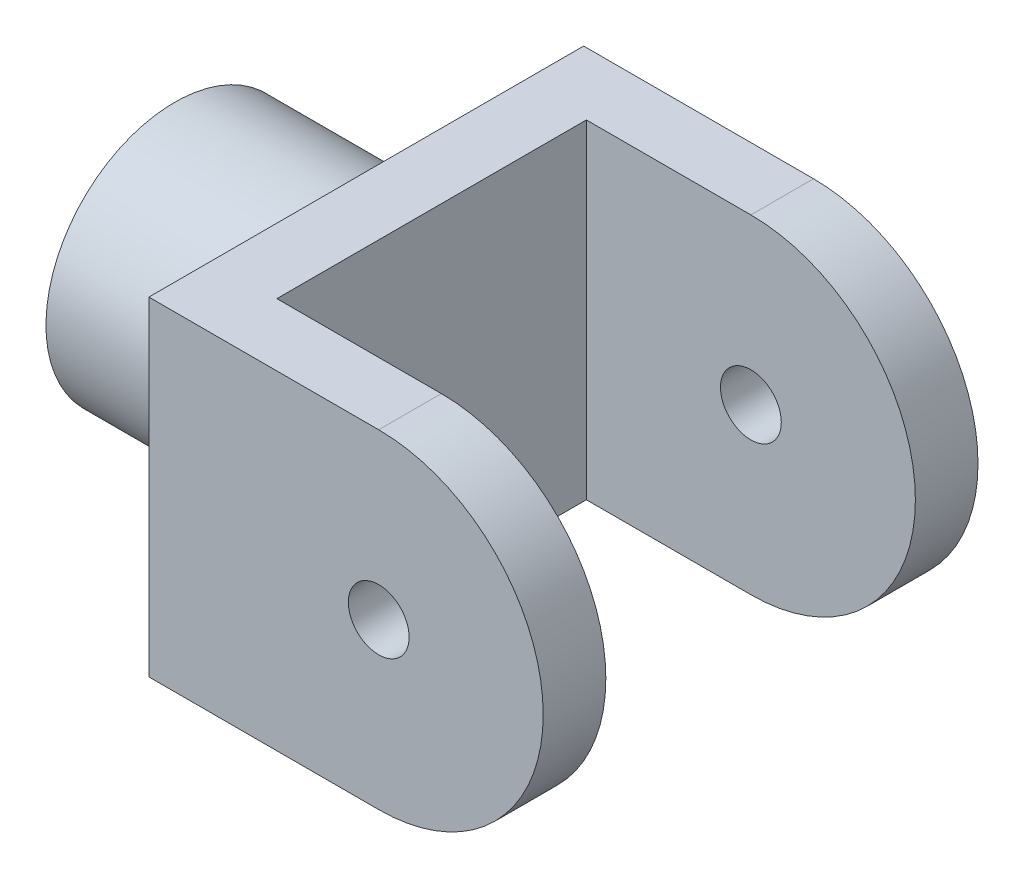
SolidWorks part; units mm, degrees
ref_plane "Front Plane" through (0, 0, 0) normal (0, 0, 1) x (1, 0, 0)
ref_plane "Top Plane" through (0, 0, 0) normal (0, 1, 0) x (1, 0, 0)
ref_plane "Right Plane" through (0, 0, 0) normal (1, 0, 0) x (0, 0, -1)
sketch "Sketch1" plane through (0, 0, 0) normal (0, 0, 1) x (1, 0, 0)
  line L0 (0, 8.5875) -> (-12, 8.5875)
  line L1 (-12, 8.5875) -> (-12, -8.5875)
  line L2 (-12, -8.5875) -> (0, -8.5875)
  circle A1 centre (0, 0) radius 1.5875
  arc A2 (0, 8.5875) -> (0, -8.5875) centre (0, 0) cw
  dimension "D1" = 3.175
  dimension "D2" = 7
  dimension "D3" = 12
extrude "Boss-Extrude2" add sketch "Sketch1" along normal blind 11.35 and the other way blind 11.35 contours L0 L1 L2 A2 | A1
sketch "Sketch3" plane through (0, 0, 0) normal (0, 0, 1) x (1, 0, 0)
  line L0 (0, 0) -> (8.5875, 0) construction
  line L1 (0, 0) -> (-8.5875, 0) construction
  line L2 (0, 8.5875) -> (-12, 8.5875) construction
  line L3 (-8.5875, 8.5875) -> (8.5875, 8.5875)
  line L4 (-8.5875, 8.5875) -> (-8.5875, -8.5875)
  line L5 (-8.5875, -8.5875) -> (8.5875, -8.5875)
  line L6 (8.5875, 8.5875) -> (8.5875, -8.5875)
  line L7 (-12, -8.5875) -> (0, -8.5875) construction
  arc A0 (0, -8.5875) -> (0, 8.5875) centre (0, 0) ccw construction
  point P15 (0, 0)
extrude "Cut-Extrude1" cut sketch "Sketch3" against normal blind 8.08 and the other way blind 8.08
sketch "Sketch4" plane through (-12, 0, 0) normal (-1, 0, 0) x (0, 0, 1)
  circle A0 centre (0, 0) radius 4.7225
  circle A1 centre (0, 0) radius 6.7225
  dimension "D1" = 9.445
  dimension "D2" = 2
extrude "Boss-Extrude4" add sketch "Sketch4" along normal blind 10
